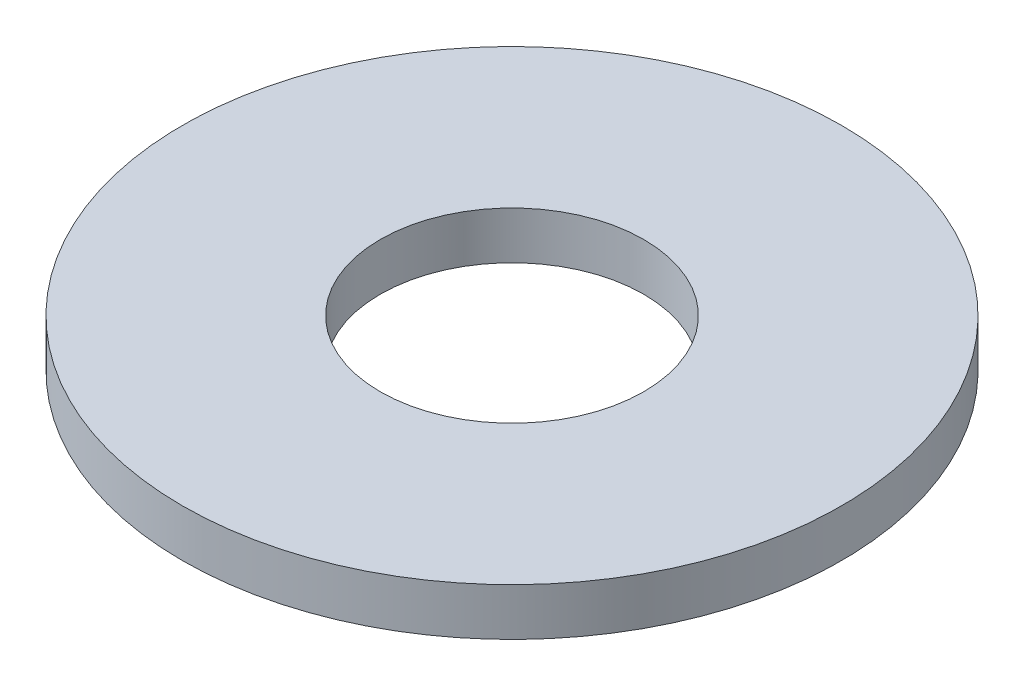
SolidWorks part; units mm, degrees
ref_plane "Front Plane" through (0, 0, 0) normal (0, 0, 1) x (1, 0, 0)
ref_plane "Top Plane" through (0, 0, 0) normal (0, 1, 0) x (1, 0, 0)
ref_plane "Right Plane" through (0, 0, 0) normal (1, 0, 0) x (0, 0, -1)
sketch "Sketch1" plane through (0, 0, 0) normal (0, 1, 0) x (1, 0, 0)
  circle A0 centre (0, 0) radius 62.5
  dimension "FLANGE_OD" = 125
extrude "Boss-Extrude1" add sketch "Sketch1" along normal blind 9
sketch "Sketch2" plane through (0, 0, 0) normal (0, 1, 0) x (1, 0, 0)
  circle A0 centre (0, 0) radius 25
  dimension "BORE_D" = 50
extrude "Cut-Extrude1" cut sketch "Sketch2" along normal through all
sketch "Sketch3" plane through (0, 9, 0) normal (0, 1, 0) x (1, 0, 0)
  circle A0 centre (0, 0) radius 16.1035 construction
  circle A1 centre (-16.1035, 0) radius 4.0022
  dimension "BOLT_D" = 8.0044
  dimension "BOLT_PCD" = 32.207
extrude "Cut-Extrude2" cut sketch "Sketch3" against normal blind 6.2737 rebuild error yes
pattern_circular "CirPattern1" count 6 over 360 rebuild error yes
